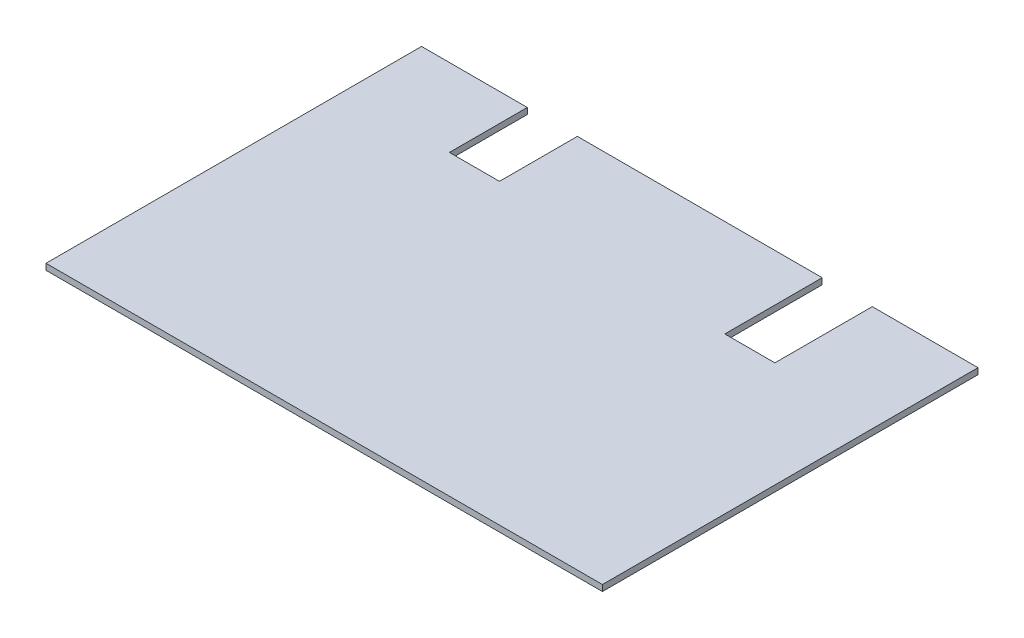
SolidWorks part; units mm, degrees
ref_plane "Front Plane" through (0, 0, 0) normal (0, 0, 1) x (1, 0, 0)
ref_plane "Top Plane" through (0, 0, 0) normal (0, 1, 0) x (1, 0, 0)
ref_plane "Right Plane" through (0, 0, 0) normal (1, 0, 0) x (0, 0, -1)
sketch "Sketch1" plane through (0, 0, 0) normal (0, 1, 0) x (1, 0, 0)
  line L1 (0, 0) -> (25.4, 0)
  line L2 (0, 0) -> (0, 17.145)
  line L3 (0, 17.145) -> (25.4, 17.145)
  line L4 (25.4, 0) -> (25.4, 17.145)
  dimension "D1" = 25.4
  dimension "D2" = 17.145
extrude "Boss-Extrude1" add sketch "Sketch1" along normal blind 0.2794
sketch "Sketch2" plane through (0, 0.2794, 0) normal (0, 1, 0) x (1, 0, 0)
  line L0 (25.4, 17.145) -> (0, 17.145) construction
  line L1 (6.0325, 17.145) -> (7.112, 17.145)
  line L2 (4.826, 14.605) -> (4.826, 13.589)
  line L3 (4.826, 13.589) -> (7.112, 13.589)
  line L4 (7.112, 17.145) -> (7.112, 13.589)
  line L5 (0, 0) -> (25.4, 0) construction
  line L6 (18.288, 17.145) -> (19.3675, 17.145)
  line L7 (18.288, 17.145) -> (18.288, 12.7)
  line L8 (18.288, 12.7) -> (20.574, 12.7)
  line L9 (20.574, 13.589) -> (20.574, 12.7)
  line L10 (0, 0) -> (25.4, 0) construction
  line L13 (20.574, 13.589) -> (20.574, 17.145)
  line L14 (20.574, 17.145) -> (19.3675, 17.145)
  line L15 (4.826, 14.605) -> (4.826, 17.145)
  line L16 (4.826, 17.145) -> (6.0325, 17.145)
  point P10 (12.7, 0)
  point P13 (12.7, 0)
  dimension "D3" = 2.286
  dimension "D4" = 2.286
  dimension "D5" = 5.588
  dimension "D6" = 5.588
extrude "Cut-Extrude1" cut sketch "Sketch2" against normal through all
